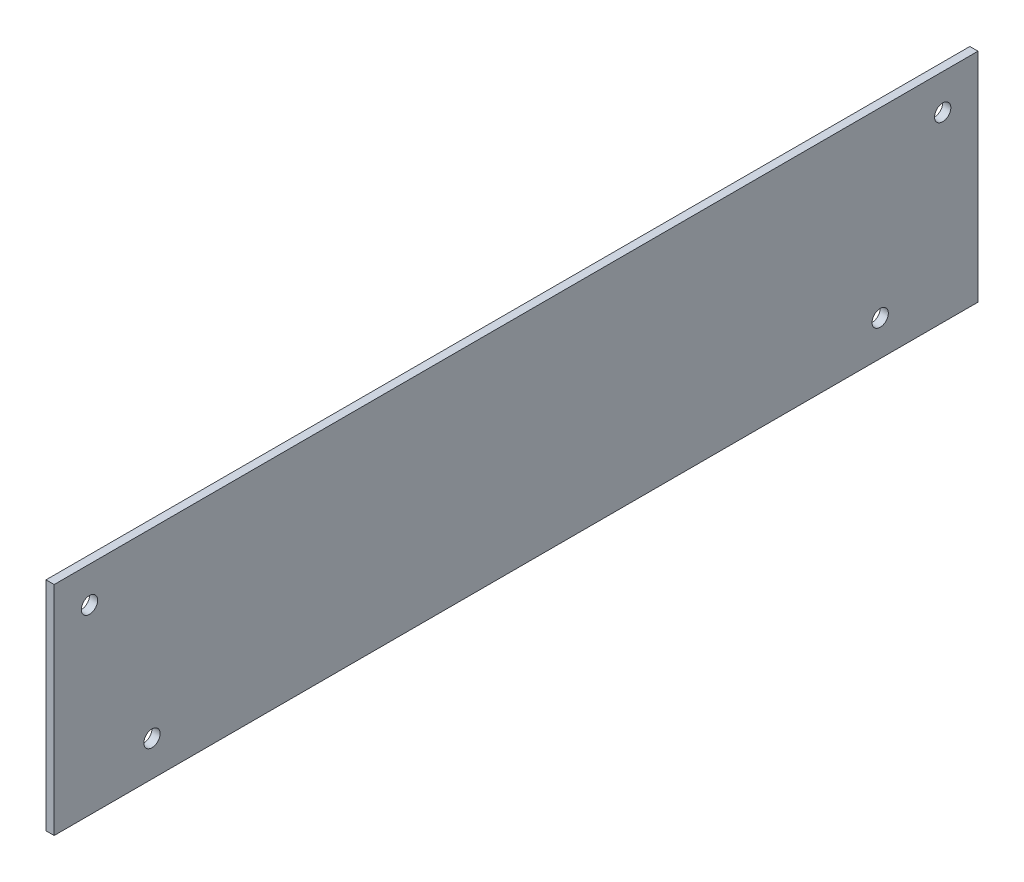
SolidWorks part; units mm, degrees
ref_plane "Front Plane" through (0, 0, 0) normal (0, 0, 1) x (1, 0, 0)
ref_plane "Top Plane" through (0, 0, 0) normal (0, 1, 0) x (1, 0, 0)
ref_plane "Right Plane" through (0, 0, 0) normal (1, 0, 0) x (0, 0, -1)
sketch "Sketch1" plane through (0, 0, 0) normal (1, 0, 0) x (0, 0, -1)
  line L1 (0, 0) -> (170, 0)
  line L2 (0, 0) -> (0, 40)
  line L3 (0, 40) -> (170, 40)
  line L4 (170, 0) -> (170, 40)
  dimension "D1" = 170
  dimension "D2" = 40
extrude "Boss-Extrude1" add sketch "Sketch1" along normal blind 1.5
sketch "Sketch2" plane through (1.5, 0, 0) normal (1, 0, 0) x (0, 0, -1)
  line L0 (0, 0) -> (170, 0) construction
  line L1 (0, 40) -> (0, 0) construction
  line L2 (170, 40) -> (0, 40) construction
  line L3 (170, 0) -> (170, 40) construction
  circle A0 centre (18, 6.5) radius 1.5
  circle A1 centre (152, 6.5) radius 1.5
  circle A2 centre (163.5, 33.5) radius 1.5
  circle A3 centre (6.5, 33.5) radius 1.5
  dimension "D1" = 6.5
  dimension "D2" = 18
  dimension "D3" = 6.5
  dimension "D4" = 6.5
  dimension "D5" = 6.5
  dimension "D6" = 6.5
  dimension "D7" = 18
  dimension "D8" = 6.5
extrude "Cut-Extrude1" cut sketch "Sketch2" against normal blind 15 and the other way blind 15
